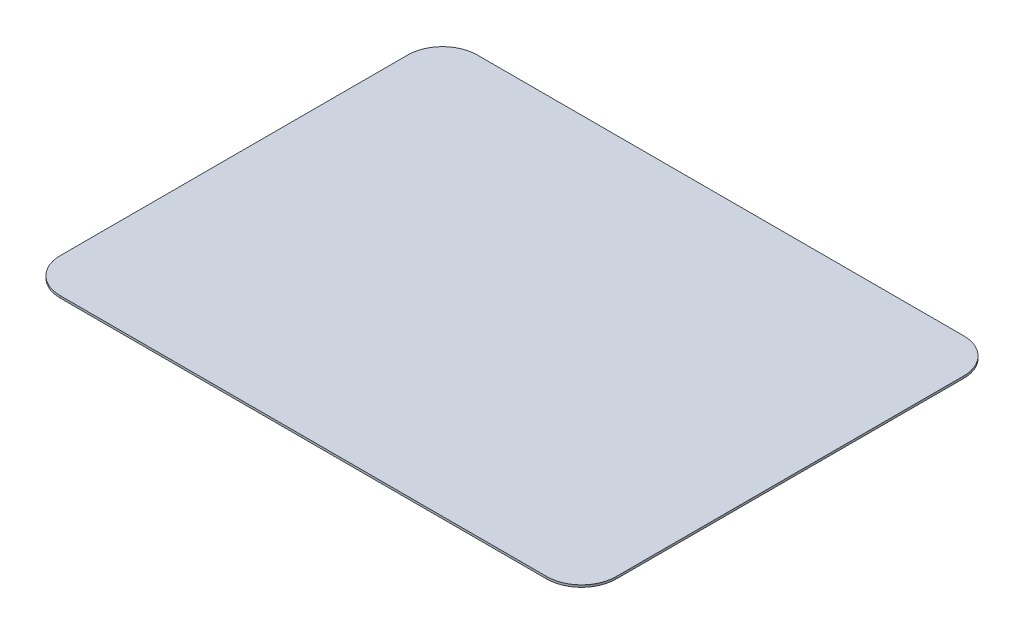
SolidWorks part; units mm, degrees
ref_plane "Front Plane" through (0, 0, 0) normal (0, 0, 1) x (1, 0, 0)
ref_plane "Top Plane" through (0, 0, 0) normal (0, 1, 0) x (1, 0, 0)
ref_plane "Right Plane" through (0, 0, 0) normal (1, 0, 0) x (0, 0, -1)
ref_plane "SheetPlane" through (0, 6.35, 0) normal (0, 1, 0) x (1, 0, 0)
sketch "Sketch1" plane through (0, 6.35, 0) normal (0, 1, 0) x (1, 0, 0)
  line L4 (101.6, -63.5) -> (101.6, 63.5)
  line L5 (88.9, 76.2) -> (-88.9, 76.2)
  line L6 (-101.6, 63.5) -> (-101.6, -63.5)
  line L7 (-88.9, -76.2) -> (88.9, -76.2)
  line L8 (101.6, -63.5) -> (101.6, 63.5)
  line L9 (88.9, 76.2) -> (-88.9, 76.2)
  line L10 (-101.6, 63.5) -> (-101.6, -63.5)
  line L11 (-88.9, -76.2) -> (88.9, -76.2)
  arc A4 (88.9, -76.2) -> (101.6, -63.5) centre (88.9, -63.5) ccw
  arc A5 (101.6, 63.5) -> (88.9, 76.2) centre (88.9, 63.5) ccw
  arc A6 (-88.9, 76.2) -> (-101.6, 63.5) centre (-88.9, 63.5) ccw
  arc A7 (-101.6, -63.5) -> (-88.9, -76.2) centre (-88.9, -63.5) ccw
  arc A8 (88.9, -76.2) -> (101.6, -63.5) centre (88.9, -63.5) ccw
  arc A9 (101.6, 63.5) -> (88.9, 76.2) centre (88.9, 63.5) ccw
  arc A10 (-88.9, 76.2) -> (-101.6, 63.5) centre (-88.9, 63.5) ccw
  arc A11 (-101.6, -63.5) -> (-88.9, -76.2) centre (-88.9, -63.5) ccw
  dimension "D1" = 0
extrude "MainBody" add sketch "Sketch1" along normal blind 0.7937
equation "\"SheetThickness\"= 0.03125in"
equation "\"D1@MainBody\" = \"SheetThickness\""
equation "\"SheetTolerance\"= 0.012in"
